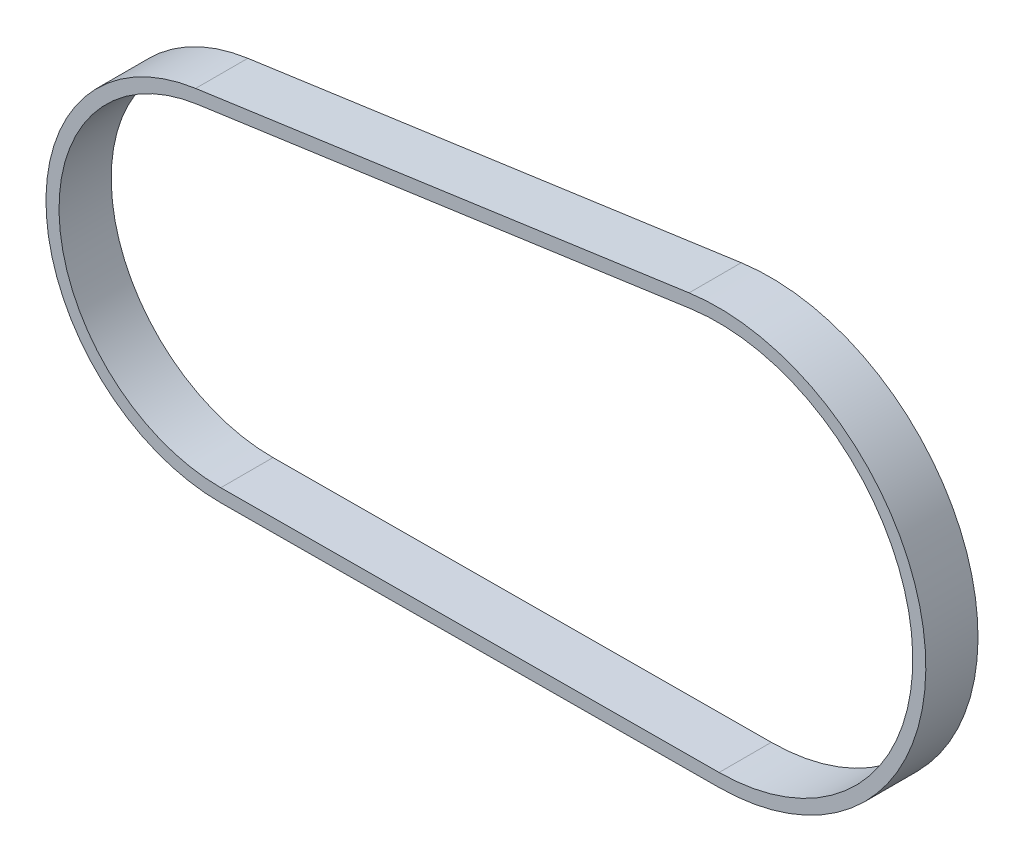
SolidWorks part; units mm, degrees
ref_plane "Front Plane" through (0, 0, 0) normal (0, 0, 1) x (1, 0, 0)
ref_plane "Top Plane" through (0, 0, 0) normal (0, 1, 0) x (1, 0, 0)
ref_plane "Right Plane" through (0, 0, 0) normal (1, 0, 0) x (0, 0, -1)
sketch "Sketch2" plane through (0, 0, 0) normal (0, 0, 1) x (1, 0, 0)
  line L0 (0, 0) -> (1, 0) construction
  line L1 (0, 0) -> (0, 1) construction
  line L6 (-2.7962, 19.8036) -> (53.922, 27.8119)
  line L7 (57.3828, -19.7053) -> (0.1028, -19.9997)
  arc A2 (53.922, 27.8119) -> (57.3828, -19.7053) centre (57.2601, 4.1704) cw
  arc A4 (0.1028, -19.9997) -> (-2.7962, 19.8036) centre (0, 0) cw
extrude "Extrude-Thin1" add sketch "Sketch2" against normal blind 6 thin thin type one direction reverse wall 1.5
